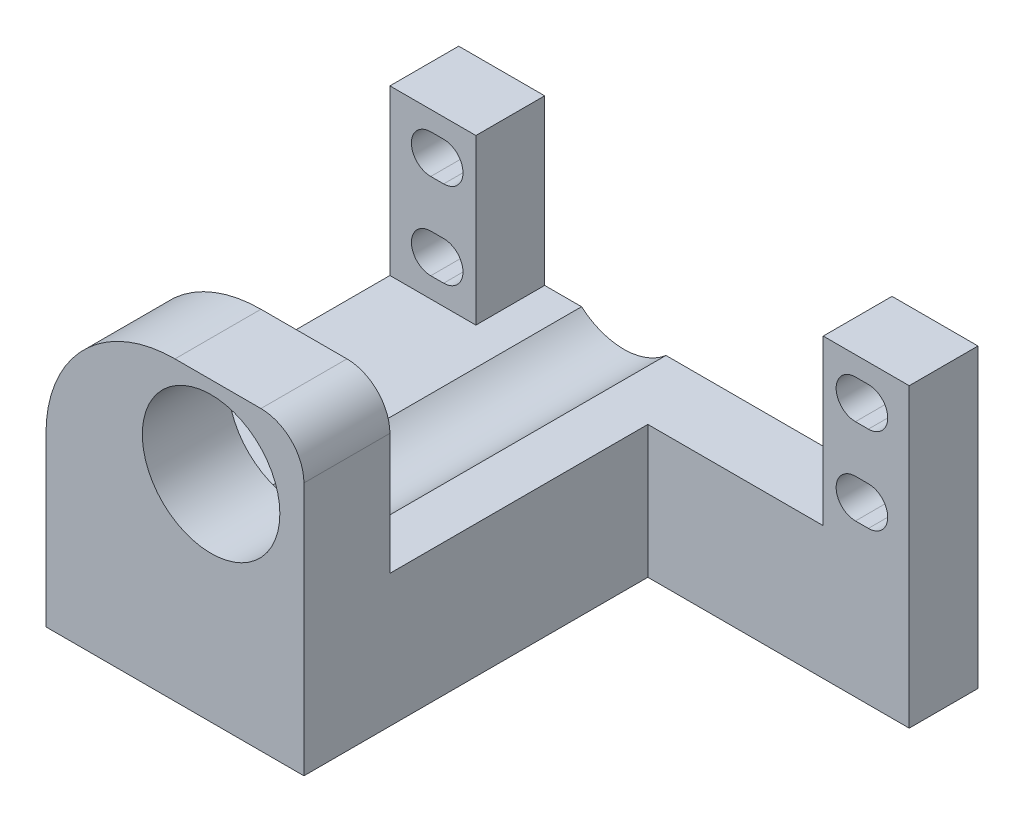
SolidWorks part; units mm, degrees
ref_plane "Front Plane" through (0, 0, 0) normal (0, 0, 1) x (1, 0, 0)
ref_plane "Top Plane" through (0, 0, 0) normal (0, 1, 0) x (1, 0, 0)
ref_plane "Right Plane" through (0, 0, 0) normal (1, 0, 0) x (0, 0, -1)
sketch "Sketch6" plane through (0, 0, 0) normal (0, 0, 1) x (1, 0, 0)
  line L0 (-16.084, 11.3857) -> (-16.084, -7.7143)
  line L1 (-16.084, -7.7143) -> (24.316, -7.7143)
  line L2 (24.316, -7.7143) -> (24.316, 11.3857)
  line L3 (24.316, 11.3857) -> (34.316, 11.3857)
  line L4 (34.316, 11.3857) -> (34.316, -23.1143)
  line L5 (34.316, -23.1143) -> (-26.084, -23.1143)
  line L6 (-26.084, -23.1143) -> (-26.084, 11.3857)
  line L7 (-26.084, 11.3857) -> (-16.084, 11.3857)
  line L8 (-20.584, 11.3857) -> (-20.584, -23.1143) construction
  line L9 (-19.834, 6.8857) -> (-21.334, 6.8857) construction
  line L10 (-19.834, 4.6357) -> (-21.334, 4.6357)
  line L11 (-19.834, 9.1357) -> (-21.334, 9.1357)
  line L12 (-19.834, -3.1143) -> (-21.334, -3.1143) construction
  line L13 (-19.834, -5.3643) -> (-21.334, -5.3643)
  line L14 (-19.834, -0.8643) -> (-21.334, -0.8643)
  line L15 (4.116, -7.7143) -> (4.116, 11.6799) construction
  line L16 (28.066, -3.1143) -> (29.566, -3.1143) construction
  line L17 (28.066, -5.3643) -> (29.566, -5.3643)
  line L18 (28.066, -0.8643) -> (29.566, -0.8643)
  line L19 (28.066, 6.8857) -> (29.566, 6.8857) construction
  line L20 (28.066, 4.6357) -> (29.566, 4.6357)
  line L21 (28.066, 9.1357) -> (29.566, 9.1357)
  arc A0 (-19.834, 4.6357) -> (-19.834, 9.1357) centre (-19.834, 6.8857) ccw
  arc A1 (-21.334, 9.1357) -> (-21.334, 4.6357) centre (-21.334, 6.8857) ccw
  arc A2 (-19.834, -5.3643) -> (-19.834, -0.8643) centre (-19.834, -3.1143) ccw
  arc A3 (-21.334, -0.8643) -> (-21.334, -5.3643) centre (-21.334, -3.1143) ccw
  arc A4 (28.066, -5.3643) -> (28.066, -0.8643) centre (28.066, -3.1143) cw
  arc A5 (29.566, -0.8643) -> (29.566, -5.3643) centre (29.566, -3.1143) cw
  arc A6 (28.066, 4.6357) -> (28.066, 9.1357) centre (28.066, 6.8857) cw
  arc A7 (29.566, 9.1357) -> (29.566, 4.6357) centre (29.566, 6.8857) cw
  point P12 (-20.584, 6.8857)
  point P18 (-20.584, -3.1143)
  point P28 (28.816, -3.1143)
  point P35 (28.816, 6.8857)
  point P40 (-16.084, 12.2857)
  dimension "D11" = 1.5
  dimension "D12" = 1.5
  dimension "D1" = 10
  dimension "D2" = 10
  dimension "D3" = 40.4
  dimension "D4" = 19.1
  dimension "D5" = 19.1
  dimension "D6" = 15.4
  dimension "D7" = 4.5
  dimension "D8" = 10
  dimension "D9" = 4.5
  dimension "D10" = 4.5
  dimension "D13" = 4.6
extrude "Boss-Extrude1" add sketch "Sketch6" along normal blind 8
sketch "Sketch7" plane through (0, 0, 8) normal (0, 0, 1) x (1, 0, 0)
  line L0 (-26.084, -23.1143) -> (34.316, -23.1143) construction
  line L1 (-26.084, -7.7143) -> (3.916, -7.7143)
  line L2 (-26.084, -7.7143) -> (-26.084, -23.1143)
  line L3 (-26.084, -23.1143) -> (3.916, -23.1143)
  line L4 (3.916, -7.7143) -> (3.916, -23.1143)
  line L5 (-26.084, 11.3857) -> (-26.084, -23.1143) construction
  line L6 (24.316, -7.7143) -> (-16.084, -7.7143) construction
  point P7 (0, 0)
  point P8 (-25.4023, -8.9464)
  point P11 (14.7803, -8.9551)
  dimension "D1" = 30
extrude "Boss-Extrude2" add sketch "Sketch7" along normal blind 40
sketch "Sketch8" plane through (0, -7.7143, 0) normal (0, 1, 0) x (1, 0, 0)
  line L0 (3.916, -48) -> (3.916, -8) construction
  line L1 (-26.084, -48) -> (3.916, -48)
  line L2 (-26.084, -48) -> (-26.084, -38)
  line L3 (-26.084, -38) -> (3.916, -38)
  line L4 (3.916, -48) -> (3.916, -38)
  dimension "D1" = 10
extrude "Boss-Extrude3" add sketch "Sketch8" along normal up to surface (19.1 mm away) up to face at (-21.084, 11.3857, 4)
sketch "Sketch9" plane through (0, 0, 48) normal (0, 0, 1) x (1, 0, 0)
  line L0 (3.916, 11.3857) -> (-26.084, 11.3857) construction
  line L1 (-26.084, 11.3857) -> (-26.084, -23.1143) construction
  circle A0 centre (-6.884, 1.8857) radius 8
  dimension "D1" = 9.5
  dimension "D2" = 19.2
  dimension "D3" = 16
extrude "Cut-Extrude1" cut sketch "Sketch9" against normal up to surface (10 mm away) up to face at (-11.084, 1.8357, 38)
fillet "Fillet2" radius 15 1 edges at (-26.084, 11.3857, 43)
fillet "Fillet3" radius 5 1 edges at (3.916, 11.3857, 43)
sketch "Sketch11" plane through (0, 0, 0) normal (0, 0, -1) x (-1, 0, 0)
  line L0 (6.884, 1.8857) -> (6.884, -25.4823) construction
  circle A1 centre (6.884, -2.0448) radius 7.5
  dimension "D1" = 15
extrude "Cut-Extrude2" cut sketch "Sketch11" against normal up to surface (38 mm away) up to face at (1.116, 1.8857, 38)
